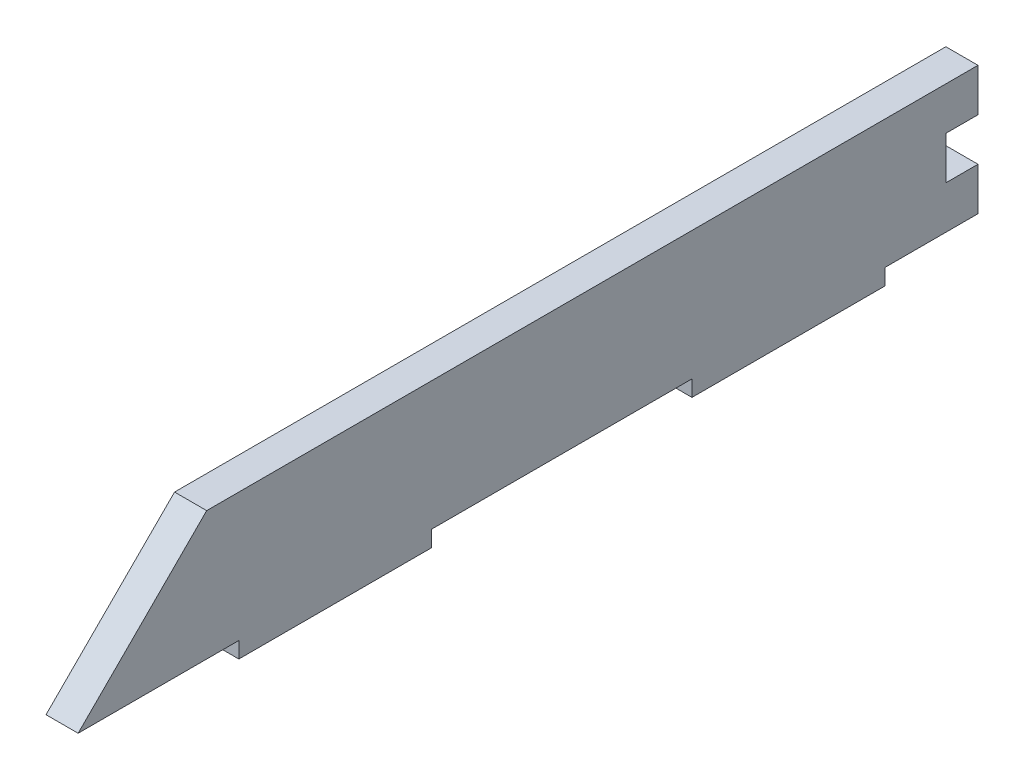
SolidWorks part; units mm, degrees
ref_plane "Front Plane" through (0, 0, 0) normal (0, 0, 1) x (1, 0, 0)
ref_plane "Top Plane" through (0, 0, 0) normal (0, 1, 0) x (1, 0, 0)
ref_plane "Right Plane" through (0, 0, 0) normal (1, 0, 0) x (0, 0, -1)
sketch "Sketch1" plane through (0, 0, 0) normal (1, 0, 0) x (0, 0, -1)
  line L1 (-177.8, -25.4) -> (177.8, -25.4)
  line L2 (-177.8, -25.4) -> (-177.8, 25.4)
  line L3 (-177.8, 25.4) -> (177.8, 25.4)
  line L4 (177.8, -25.4) -> (177.8, 25.4)
  line L5 (-177.8, -25.4) -> (177.8, 25.4) construction
  line L6 (-177.8, 25.4) -> (177.8, -25.4) construction
  point P0 (0, 0)
  dimension "D1" = 355.6
  dimension "D2" = 50.8
extrude "Boss-Extrude1" add sketch "Sketch1" along normal blind 12.7
sketch "Sketch2" plane through (12.7, 0, 0) normal (1, 0, 0) x (0, 0, -1)
  line L0 (-177.8, -25.4) -> (-127, 25.4)
  line L1 (177.8, 25.4) -> (-177.8, 25.4) construction
  dimension "D1" = 50.8
extrude "Cut-Extrude1" cut sketch "Sketch2" against normal through all and the other way through all
sketch "Sketch3" plane through (0, 0, 0) normal (-1, 0, 0) x (0, 0, 1)
  line L0 (177.8, -25.4) -> (-177.8, -25.4) construction
  line L1 (-140.97, -25.4) -> (-64.77, -25.4)
  line L2 (-140.97, -25.4) -> (-140.97, -31.75)
  line L3 (-140.97, -31.75) -> (-64.77, -31.75)
  line L4 (-64.77, -25.4) -> (-64.77, -31.75)
  line L5 (-177.8, -25.4) -> (-177.8, 25.4) construction
  line L6 (38.1, -25.4) -> (114.3, -25.4)
  line L7 (38.1, -25.4) -> (38.1, -31.75)
  line L8 (38.1, -31.75) -> (114.3, -31.75)
  line L9 (114.3, -25.4) -> (114.3, -31.75)
  dimension "D1" = 76.2
  dimension "D2" = 6.35
  dimension "D3" = 76.2
  dimension "D4" = 6.35
  dimension "D5" = 36.83
  dimension "D6" = 215.9
extrude "Boss-Extrude2" add sketch "Sketch3" against normal blind 12.7
sketch "Sketch4" plane through (0, 0, 0) normal (-1, 0, 0) x (0, 0, 1)
  line L0 (-177.8, -25.4) -> (-177.8, 25.4) construction
  line L1 (-177.8, 8.4667) -> (-165.1, 8.4667)
  line L2 (-177.8, 8.4667) -> (-177.8, -8.4667)
  line L3 (-177.8, -8.4667) -> (-165.1, -8.4667)
  line L4 (-165.1, 8.4667) -> (-165.1, -8.4667)
  line L5 (-140.97, -25.4) -> (-177.8, -25.4) construction
  dimension "D1" = 16.9333
  dimension "D2" = 16.9333
  dimension "D3" = 12.7
extrude "Cut-Extrude2" cut sketch "Sketch4" against normal through all
